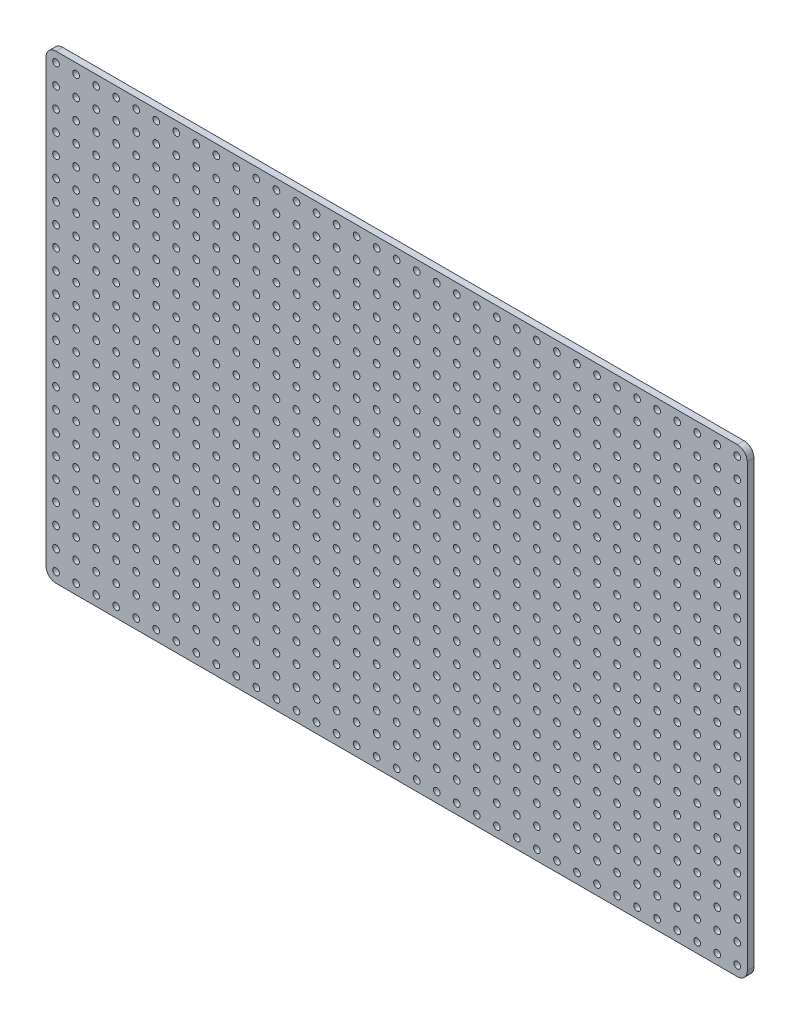
SolidWorks part; units mm, degrees
ref_plane "Alzado" through (0, 0, 0) normal (0, 0, 1) x (1, 0, 0)
ref_plane "Planta" through (0, 0, 0) normal (0, 1, 0) x (1, 0, 0)
ref_plane "Vista lateral" through (0, 0, 0) normal (1, 0, 0) x (0, 0, -1)
sketch "Model" plane through (0, 0, 0) normal (0, 0, 1) x (1, 0, 0)
  line L0 (256.4291, 471.7422) -> (562.4291, 471.7422)
  line L1 (256.4291, 264.7422) -> (562.4291, 264.7422)
  line L2 (251.9291, 269.2422) -> (251.9291, 467.2422)
  line L3 (566.9291, 467.2422) -> (566.9291, 269.2422)
  arc A0 (566.9291, 467.2422) -> (562.4291, 471.7422) centre (562.4291, 467.2422) ccw
  arc A1 (256.4291, 471.7422) -> (251.9291, 467.2422) centre (256.4291, 467.2422) ccw
  arc A2 (562.4291, 264.7422) -> (566.9291, 269.2422) centre (562.4291, 269.2422) ccw
  arc A3 (251.9291, 269.2422) -> (256.4291, 264.7422) centre (256.4291, 269.2422) ccw
  circle A4 centre (256.4291, 467.2422) radius 1.5
  circle A5 centre (256.4291, 458.2422) radius 1.5
  circle A6 centre (256.4291, 449.2422) radius 1.5
  circle A7 centre (256.4291, 440.2422) radius 1.5
  circle A8 centre (256.4291, 431.2422) radius 1.5
  circle A9 centre (256.4291, 422.2422) radius 1.5
  circle A10 centre (256.4291, 413.2422) radius 1.5
  circle A11 centre (256.4291, 404.2422) radius 1.5
  circle A12 centre (256.4291, 395.2422) radius 1.5
  circle A13 centre (256.4291, 386.2422) radius 1.5
  circle A14 centre (256.4291, 377.2422) radius 1.5
  circle A15 centre (256.4291, 368.2422) radius 1.5
  circle A16 centre (256.4291, 359.2422) radius 1.5
  circle A17 centre (256.4291, 350.2422) radius 1.5
  circle A18 centre (256.4291, 341.2422) radius 1.5
  circle A19 centre (256.4291, 332.2422) radius 1.5
  circle A20 centre (256.4291, 323.2422) radius 1.5
  circle A21 centre (256.4291, 314.2422) radius 1.5
  circle A22 centre (256.4291, 305.2422) radius 1.5
  circle A23 centre (265.4291, 467.2422) radius 1.5
  circle A24 centre (265.4291, 458.2422) radius 1.5
  circle A25 centre (265.4291, 449.2422) radius 1.5
  circle A26 centre (265.4291, 440.2422) radius 1.5
  circle A27 centre (265.4291, 431.2422) radius 1.5
  circle A28 centre (265.4291, 422.2422) radius 1.5
  circle A29 centre (265.4291, 413.2422) radius 1.5
  circle A30 centre (265.4291, 404.2422) radius 1.5
  circle A31 centre (265.4291, 395.2422) radius 1.5
  circle A32 centre (265.4291, 386.2422) radius 1.5
  circle A33 centre (265.4291, 377.2422) radius 1.5
  circle A34 centre (265.4291, 368.2422) radius 1.5
  circle A35 centre (265.4291, 359.2422) radius 1.5
  circle A36 centre (265.4291, 350.2422) radius 1.5
  circle A37 centre (265.4291, 341.2422) radius 1.5
  circle A38 centre (265.4291, 332.2422) radius 1.5
  circle A39 centre (265.4291, 323.2422) radius 1.5
  circle A40 centre (265.4291, 314.2422) radius 1.5
  circle A41 centre (265.4291, 305.2422) radius 1.5
  circle A42 centre (274.4291, 467.2422) radius 1.5
  circle A43 centre (274.4291, 458.2422) radius 1.5
  circle A44 centre (274.4291, 449.2422) radius 1.5
  circle A45 centre (274.4291, 440.2422) radius 1.5
  circle A46 centre (274.4291, 431.2422) radius 1.5
  circle A47 centre (274.4291, 422.2422) radius 1.5
  circle A48 centre (274.4291, 413.2422) radius 1.5
  circle A49 centre (274.4291, 404.2422) radius 1.5
  circle A50 centre (274.4291, 395.2422) radius 1.5
  circle A51 centre (274.4291, 386.2422) radius 1.5
  circle A52 centre (274.4291, 377.2422) radius 1.5
  circle A53 centre (274.4291, 368.2422) radius 1.5
  circle A54 centre (274.4291, 359.2422) radius 1.5
  circle A55 centre (274.4291, 350.2422) radius 1.5
  circle A56 centre (274.4291, 341.2422) radius 1.5
  circle A57 centre (274.4291, 332.2422) radius 1.5
  circle A58 centre (274.4291, 323.2422) radius 1.5
  circle A59 centre (274.4291, 314.2422) radius 1.5
  circle A60 centre (274.4291, 305.2422) radius 1.5
  circle A61 centre (283.4291, 467.2422) radius 1.5
  circle A62 centre (283.4291, 458.2422) radius 1.5
  circle A63 centre (283.4291, 449.2422) radius 1.5
  circle A64 centre (283.4291, 440.2422) radius 1.5
  circle A65 centre (283.4291, 431.2422) radius 1.5
  circle A66 centre (283.4291, 422.2422) radius 1.5
  circle A67 centre (283.4291, 413.2422) radius 1.5
  circle A68 centre (283.4291, 404.2422) radius 1.5
  circle A69 centre (283.4291, 395.2422) radius 1.5
  circle A70 centre (283.4291, 386.2422) radius 1.5
  circle A71 centre (283.4291, 377.2422) radius 1.5
  circle A72 centre (283.4291, 368.2422) radius 1.5
  circle A73 centre (283.4291, 359.2422) radius 1.5
  circle A74 centre (283.4291, 350.2422) radius 1.5
  circle A75 centre (283.4291, 341.2422) radius 1.5
  circle A76 centre (283.4291, 332.2422) radius 1.5
  circle A77 centre (283.4291, 323.2422) radius 1.5
  circle A78 centre (283.4291, 314.2422) radius 1.5
  circle A79 centre (283.4291, 305.2422) radius 1.5
  circle A80 centre (292.4291, 467.2422) radius 1.5
  circle A81 centre (292.4291, 458.2422) radius 1.5
  circle A82 centre (292.4291, 449.2422) radius 1.5
  circle A83 centre (292.4291, 440.2422) radius 1.5
  circle A84 centre (292.4291, 431.2422) radius 1.5
  circle A85 centre (292.4291, 422.2422) radius 1.5
  circle A86 centre (292.4291, 413.2422) radius 1.5
  circle A87 centre (292.4291, 404.2422) radius 1.5
  circle A88 centre (292.4291, 395.2422) radius 1.5
  circle A89 centre (292.4291, 386.2422) radius 1.5
  circle A90 centre (292.4291, 377.2422) radius 1.5
  circle A91 centre (292.4291, 368.2422) radius 1.5
  circle A92 centre (292.4291, 359.2422) radius 1.5
  circle A93 centre (292.4291, 350.2422) radius 1.5
  circle A94 centre (292.4291, 341.2422) radius 1.5
  circle A95 centre (292.4291, 332.2422) radius 1.5
  circle A96 centre (292.4291, 323.2422) radius 1.5
  circle A97 centre (292.4291, 314.2422) radius 1.5
  circle A98 centre (292.4291, 305.2422) radius 1.5
  circle A99 centre (301.4291, 467.2422) radius 1.5
  circle A100 centre (301.4291, 458.2422) radius 1.5
  circle A101 centre (301.4291, 449.2422) radius 1.5
  circle A102 centre (301.4291, 440.2422) radius 1.5
  circle A103 centre (301.4291, 431.2422) radius 1.5
  circle A104 centre (301.4291, 422.2422) radius 1.5
  circle A105 centre (301.4291, 413.2422) radius 1.5
  circle A106 centre (301.4291, 404.2422) radius 1.5
  circle A107 centre (301.4291, 395.2422) radius 1.5
  circle A108 centre (301.4291, 386.2422) radius 1.5
  circle A109 centre (301.4291, 377.2422) radius 1.5
  circle A110 centre (301.4291, 368.2422) radius 1.5
  circle A111 centre (301.4291, 359.2422) radius 1.5
  circle A112 centre (301.4291, 350.2422) radius 1.5
  circle A113 centre (301.4291, 341.2422) radius 1.5
  circle A114 centre (301.4291, 332.2422) radius 1.5
  circle A115 centre (301.4291, 323.2422) radius 1.5
  circle A116 centre (301.4291, 314.2422) radius 1.5
  circle A117 centre (301.4291, 305.2422) radius 1.5
  circle A118 centre (310.4291, 467.2422) radius 1.5
  circle A119 centre (310.4291, 458.2422) radius 1.5
  circle A120 centre (310.4291, 449.2422) radius 1.5
  circle A121 centre (310.4291, 440.2422) radius 1.5
  circle A122 centre (310.4291, 431.2422) radius 1.5
  circle A123 centre (310.4291, 422.2422) radius 1.5
  circle A124 centre (310.4291, 413.2422) radius 1.5
  circle A125 centre (310.4291, 404.2422) radius 1.5
  circle A126 centre (310.4291, 395.2422) radius 1.5
  circle A127 centre (310.4291, 386.2422) radius 1.5
  circle A128 centre (310.4291, 377.2422) radius 1.5
  circle A129 centre (310.4291, 368.2422) radius 1.5
  circle A130 centre (310.4291, 359.2422) radius 1.5
  circle A131 centre (310.4291, 350.2422) radius 1.5
  circle A132 centre (310.4291, 341.2422) radius 1.5
  circle A133 centre (310.4291, 332.2422) radius 1.5
  circle A134 centre (310.4291, 323.2422) radius 1.5
  circle A135 centre (310.4291, 314.2422) radius 1.5
  circle A136 centre (310.4291, 305.2422) radius 1.5
  circle A137 centre (319.4291, 467.2422) radius 1.5
  circle A138 centre (319.4291, 458.2422) radius 1.5
  circle A139 centre (319.4291, 449.2422) radius 1.5
  circle A140 centre (319.4291, 440.2422) radius 1.5
  circle A141 centre (319.4291, 431.2422) radius 1.5
  circle A142 centre (319.4291, 422.2422) radius 1.5
  circle A143 centre (319.4291, 413.2422) radius 1.5
  circle A144 centre (319.4291, 404.2422) radius 1.5
  circle A145 centre (319.4291, 395.2422) radius 1.5
  circle A146 centre (319.4291, 386.2422) radius 1.5
  circle A147 centre (319.4291, 377.2422) radius 1.5
  circle A148 centre (319.4291, 368.2422) radius 1.5
  circle A149 centre (319.4291, 359.2422) radius 1.5
  circle A150 centre (319.4291, 350.2422) radius 1.5
  circle A151 centre (319.4291, 341.2422) radius 1.5
  circle A152 centre (319.4291, 332.2422) radius 1.5
  circle A153 centre (319.4291, 323.2422) radius 1.5
  circle A154 centre (319.4291, 314.2422) radius 1.5
  circle A155 centre (319.4291, 305.2422) radius 1.5
  circle A156 centre (328.4291, 467.2422) radius 1.5
  circle A157 centre (328.4291, 458.2422) radius 1.5
  circle A158 centre (328.4291, 449.2422) radius 1.5
  circle A159 centre (328.4291, 440.2422) radius 1.5
  circle A160 centre (328.4291, 431.2422) radius 1.5
  circle A161 centre (328.4291, 422.2422) radius 1.5
  circle A162 centre (328.4291, 413.2422) radius 1.5
  circle A163 centre (328.4291, 404.2422) radius 1.5
  circle A164 centre (328.4291, 395.2422) radius 1.5
  circle A165 centre (328.4291, 386.2422) radius 1.5
  circle A166 centre (328.4291, 377.2422) radius 1.5
  circle A167 centre (328.4291, 368.2422) radius 1.5
  circle A168 centre (328.4291, 359.2422) radius 1.5
  circle A169 centre (328.4291, 350.2422) radius 1.5
  circle A170 centre (328.4291, 341.2422) radius 1.5
  circle A171 centre (328.4291, 332.2422) radius 1.5
  circle A172 centre (328.4291, 323.2422) radius 1.5
  circle A173 centre (328.4291, 314.2422) radius 1.5
  circle A174 centre (328.4291, 305.2422) radius 1.5
  circle A175 centre (337.4291, 467.2422) radius 1.5
  circle A176 centre (337.4291, 458.2422) radius 1.5
  circle A177 centre (337.4291, 449.2422) radius 1.5
  circle A178 centre (337.4291, 440.2422) radius 1.5
  circle A179 centre (337.4291, 431.2422) radius 1.5
  circle A180 centre (337.4291, 422.2422) radius 1.5
  circle A181 centre (337.4291, 413.2422) radius 1.5
  circle A182 centre (337.4291, 404.2422) radius 1.5
  circle A183 centre (337.4291, 395.2422) radius 1.5
  circle A184 centre (337.4291, 386.2422) radius 1.5
  circle A185 centre (337.4291, 377.2422) radius 1.5
  circle A186 centre (337.4291, 368.2422) radius 1.5
  circle A187 centre (337.4291, 359.2422) radius 1.5
  circle A188 centre (337.4291, 350.2422) radius 1.5
  circle A189 centre (337.4291, 341.2422) radius 1.5
  circle A190 centre (337.4291, 332.2422) radius 1.5
  circle A191 centre (337.4291, 323.2422) radius 1.5
  circle A192 centre (337.4291, 314.2422) radius 1.5
  circle A193 centre (337.4291, 305.2422) radius 1.5
  circle A194 centre (346.4291, 467.2422) radius 1.5
  circle A195 centre (346.4291, 458.2422) radius 1.5
  circle A196 centre (346.4291, 449.2422) radius 1.5
  circle A197 centre (346.4291, 440.2422) radius 1.5
  circle A198 centre (346.4291, 431.2422) radius 1.5
  circle A199 centre (346.4291, 422.2422) radius 1.5
  circle A200 centre (346.4291, 413.2422) radius 1.5
  circle A201 centre (346.4291, 404.2422) radius 1.5
  circle A202 centre (346.4291, 395.2422) radius 1.5
  circle A203 centre (346.4291, 386.2422) radius 1.5
  circle A204 centre (346.4291, 377.2422) radius 1.5
  circle A205 centre (346.4291, 368.2422) radius 1.5
  circle A206 centre (346.4291, 359.2422) radius 1.5
  circle A207 centre (346.4291, 350.2422) radius 1.5
  circle A208 centre (346.4291, 341.2422) radius 1.5
  circle A209 centre (346.4291, 332.2422) radius 1.5
  circle A210 centre (346.4291, 323.2422) radius 1.5
  circle A211 centre (346.4291, 314.2422) radius 1.5
  circle A212 centre (346.4291, 305.2422) radius 1.5
  circle A213 centre (355.4291, 467.2422) radius 1.5
  circle A214 centre (355.4291, 458.2422) radius 1.5
  circle A215 centre (355.4291, 449.2422) radius 1.5
  circle A216 centre (355.4291, 440.2422) radius 1.5
  circle A217 centre (355.4291, 431.2422) radius 1.5
  circle A218 centre (355.4291, 422.2422) radius 1.5
  circle A219 centre (355.4291, 413.2422) radius 1.5
  circle A220 centre (355.4291, 404.2422) radius 1.5
  circle A221 centre (355.4291, 395.2422) radius 1.5
  circle A222 centre (355.4291, 386.2422) radius 1.5
  circle A223 centre (355.4291, 377.2422) radius 1.5
  circle A224 centre (355.4291, 368.2422) radius 1.5
  circle A225 centre (355.4291, 359.2422) radius 1.5
  circle A226 centre (355.4291, 350.2422) radius 1.5
  circle A227 centre (355.4291, 341.2422) radius 1.5
  circle A228 centre (355.4291, 332.2422) radius 1.5
  circle A229 centre (355.4291, 323.2422) radius 1.5
  circle A230 centre (355.4291, 314.2422) radius 1.5
  circle A231 centre (355.4291, 305.2422) radius 1.5
  circle A232 centre (364.4291, 467.2422) radius 1.5
  circle A233 centre (364.4291, 458.2422) radius 1.5
  circle A234 centre (364.4291, 449.2422) radius 1.5
  circle A235 centre (364.4291, 440.2422) radius 1.5
  circle A236 centre (364.4291, 431.2422) radius 1.5
  circle A237 centre (364.4291, 422.2422) radius 1.5
  circle A238 centre (364.4291, 413.2422) radius 1.5
  circle A239 centre (364.4291, 404.2422) radius 1.5
  circle A240 centre (364.4291, 395.2422) radius 1.5
  circle A241 centre (364.4291, 386.2422) radius 1.5
  circle A242 centre (364.4291, 377.2422) radius 1.5
  circle A243 centre (364.4291, 368.2422) radius 1.5
  circle A244 centre (364.4291, 359.2422) radius 1.5
  circle A245 centre (364.4291, 350.2422) radius 1.5
  circle A246 centre (364.4291, 341.2422) radius 1.5
  circle A247 centre (364.4291, 332.2422) radius 1.5
  circle A248 centre (364.4291, 323.2422) radius 1.5
  circle A249 centre (364.4291, 314.2422) radius 1.5
  circle A250 centre (364.4291, 305.2422) radius 1.5
  circle A251 centre (373.4291, 467.2422) radius 1.5
  circle A252 centre (373.4291, 458.2422) radius 1.5
  circle A253 centre (373.4291, 449.2422) radius 1.5
  circle A254 centre (373.4291, 440.2422) radius 1.5
  circle A255 centre (373.4291, 431.2422) radius 1.5
  circle A256 centre (373.4291, 422.2422) radius 1.5
  circle A257 centre (373.4291, 413.2422) radius 1.5
  circle A258 centre (373.4291, 404.2422) radius 1.5
  circle A259 centre (373.4291, 395.2422) radius 1.5
  circle A260 centre (373.4291, 386.2422) radius 1.5
  circle A261 centre (373.4291, 377.2422) radius 1.5
  circle A262 centre (373.4291, 368.2422) radius 1.5
  circle A263 centre (373.4291, 359.2422) radius 1.5
  circle A264 centre (373.4291, 350.2422) radius 1.5
  circle A265 centre (373.4291, 341.2422) radius 1.5
  circle A266 centre (373.4291, 332.2422) radius 1.5
  circle A267 centre (373.4291, 323.2422) radius 1.5
  circle A268 centre (373.4291, 314.2422) radius 1.5
  circle A269 centre (373.4291, 305.2422) radius 1.5
  circle A270 centre (382.4291, 467.2422) radius 1.5
  circle A271 centre (382.4291, 458.2422) radius 1.5
  circle A272 centre (382.4291, 449.2422) radius 1.5
  circle A273 centre (382.4291, 440.2422) radius 1.5
  circle A274 centre (382.4291, 431.2422) radius 1.5
  circle A275 centre (382.4291, 422.2422) radius 1.5
  circle A276 centre (382.4291, 413.2422) radius 1.5
  circle A277 centre (382.4291, 404.2422) radius 1.5
  circle A278 centre (382.4291, 395.2422) radius 1.5
  circle A279 centre (382.4291, 386.2422) radius 1.5
  circle A280 centre (382.4291, 377.2422) radius 1.5
  circle A281 centre (382.4291, 368.2422) radius 1.5
  circle A282 centre (382.4291, 359.2422) radius 1.5
  circle A283 centre (382.4291, 350.2422) radius 1.5
  circle A284 centre (382.4291, 341.2422) radius 1.5
  circle A285 centre (382.4291, 332.2422) radius 1.5
  circle A286 centre (382.4291, 323.2422) radius 1.5
  circle A287 centre (382.4291, 314.2422) radius 1.5
  circle A288 centre (382.4291, 305.2422) radius 1.5
  circle A289 centre (391.4291, 467.2422) radius 1.5
  circle A290 centre (391.4291, 458.2422) radius 1.5
  circle A291 centre (391.4291, 449.2422) radius 1.5
  circle A292 centre (391.4291, 440.2422) radius 1.5
  circle A293 centre (391.4291, 431.2422) radius 1.5
  circle A294 centre (391.4291, 422.2422) radius 1.5
  circle A295 centre (391.4291, 413.2422) radius 1.5
  circle A296 centre (391.4291, 404.2422) radius 1.5
  circle A297 centre (391.4291, 395.2422) radius 1.5
  circle A298 centre (391.4291, 386.2422) radius 1.5
  circle A299 centre (391.4291, 377.2422) radius 1.5
  circle A300 centre (391.4291, 368.2422) radius 1.5
  circle A301 centre (391.4291, 359.2422) radius 1.5
  circle A302 centre (391.4291, 350.2422) radius 1.5
  circle A303 centre (391.4291, 341.2422) radius 1.5
  circle A304 centre (391.4291, 332.2422) radius 1.5
  circle A305 centre (391.4291, 323.2422) radius 1.5
  circle A306 centre (391.4291, 314.2422) radius 1.5
  circle A307 centre (391.4291, 305.2422) radius 1.5
  circle A308 centre (400.4291, 467.2422) radius 1.5
  circle A309 centre (400.4291, 458.2422) radius 1.5
  circle A310 centre (400.4291, 449.2422) radius 1.5
  circle A311 centre (400.4291, 440.2422) radius 1.5
  circle A312 centre (400.4291, 431.2422) radius 1.5
  circle A313 centre (400.4291, 422.2422) radius 1.5
  circle A314 centre (400.4291, 413.2422) radius 1.5
  circle A315 centre (400.4291, 404.2422) radius 1.5
  circle A316 centre (400.4291, 395.2422) radius 1.5
  circle A317 centre (400.4291, 386.2422) radius 1.5
  circle A318 centre (400.4291, 377.2422) radius 1.5
  circle A319 centre (400.4291, 368.2422) radius 1.5
  circle A320 centre (400.4291, 359.2422) radius 1.5
  circle A321 centre (400.4291, 350.2422) radius 1.5
  circle A322 centre (400.4291, 341.2422) radius 1.5
  circle A323 centre (400.4291, 332.2422) radius 1.5
  circle A324 centre (400.4291, 323.2422) radius 1.5
  circle A325 centre (400.4291, 314.2422) radius 1.5
  circle A326 centre (400.4291, 305.2422) radius 1.5
  circle A327 centre (409.4291, 467.2422) radius 1.5
  circle A328 centre (409.4291, 458.2422) radius 1.5
  circle A329 centre (409.4291, 449.2422) radius 1.5
  circle A330 centre (409.4291, 440.2422) radius 1.5
  circle A331 centre (409.4291, 431.2422) radius 1.5
  circle A332 centre (409.4291, 422.2422) radius 1.5
  circle A333 centre (409.4291, 413.2422) radius 1.5
  circle A334 centre (409.4291, 404.2422) radius 1.5
  circle A335 centre (409.4291, 395.2422) radius 1.5
  circle A336 centre (409.4291, 386.2422) radius 1.5
  circle A337 centre (409.4291, 377.2422) radius 1.5
  circle A338 centre (409.4291, 368.2422) radius 1.5
  circle A339 centre (409.4291, 359.2422) radius 1.5
  circle A340 centre (409.4291, 350.2422) radius 1.5
  circle A341 centre (409.4291, 341.2422) radius 1.5
  circle A342 centre (409.4291, 332.2422) radius 1.5
  circle A343 centre (409.4291, 323.2422) radius 1.5
  circle A344 centre (409.4291, 314.2422) radius 1.5
  circle A345 centre (409.4291, 305.2422) radius 1.5
  circle A346 centre (418.4291, 467.2422) radius 1.5
  circle A347 centre (418.4291, 458.2422) radius 1.5
  circle A348 centre (418.4291, 449.2422) radius 1.5
  circle A349 centre (418.4291, 440.2422) radius 1.5
  circle A350 centre (418.4291, 431.2422) radius 1.5
  circle A351 centre (418.4291, 422.2422) radius 1.5
  circle A352 centre (418.4291, 413.2422) radius 1.5
  circle A353 centre (418.4291, 404.2422) radius 1.5
  circle A354 centre (418.4291, 395.2422) radius 1.5
  circle A355 centre (418.4291, 386.2422) radius 1.5
  circle A356 centre (418.4291, 377.2422) radius 1.5
  circle A357 centre (418.4291, 368.2422) radius 1.5
  circle A358 centre (418.4291, 359.2422) radius 1.5
  circle A359 centre (418.4291, 350.2422) radius 1.5
  circle A360 centre (418.4291, 341.2422) radius 1.5
  circle A361 centre (418.4291, 332.2422) radius 1.5
  circle A362 centre (418.4291, 323.2422) radius 1.5
  circle A363 centre (418.4291, 314.2422) radius 1.5
  circle A364 centre (418.4291, 305.2422) radius 1.5
  circle A365 centre (427.4291, 467.2422) radius 1.5
  circle A366 centre (427.4291, 458.2422) radius 1.5
  circle A367 centre (427.4291, 449.2422) radius 1.5
  circle A368 centre (427.4291, 440.2422) radius 1.5
  circle A369 centre (427.4291, 431.2422) radius 1.5
  circle A370 centre (427.4291, 422.2422) radius 1.5
  circle A371 centre (427.4291, 413.2422) radius 1.5
  circle A372 centre (427.4291, 404.2422) radius 1.5
  circle A373 centre (427.4291, 395.2422) radius 1.5
  circle A374 centre (427.4291, 386.2422) radius 1.5
  circle A375 centre (427.4291, 377.2422) radius 1.5
  circle A376 centre (427.4291, 368.2422) radius 1.5
  circle A377 centre (427.4291, 359.2422) radius 1.5
  circle A378 centre (427.4291, 350.2422) radius 1.5
  circle A379 centre (427.4291, 341.2422) radius 1.5
  circle A380 centre (427.4291, 332.2422) radius 1.5
  circle A381 centre (427.4291, 323.2422) radius 1.5
  circle A382 centre (427.4291, 314.2422) radius 1.5
  circle A383 centre (427.4291, 305.2422) radius 1.5
  circle A384 centre (436.4291, 467.2422) radius 1.5
  circle A385 centre (436.4291, 458.2422) radius 1.5
  circle A386 centre (436.4291, 449.2422) radius 1.5
  circle A387 centre (436.4291, 440.2422) radius 1.5
  circle A388 centre (436.4291, 431.2422) radius 1.5
  circle A389 centre (436.4291, 422.2422) radius 1.5
  circle A390 centre (436.4291, 413.2422) radius 1.5
  circle A391 centre (436.4291, 404.2422) radius 1.5
  circle A392 centre (436.4291, 395.2422) radius 1.5
  circle A393 centre (436.4291, 386.2422) radius 1.5
  circle A394 centre (436.4291, 377.2422) radius 1.5
  circle A395 centre (436.4291, 368.2422) radius 1.5
  circle A396 centre (436.4291, 359.2422) radius 1.5
  circle A397 centre (436.4291, 350.2422) radius 1.5
  circle A398 centre (436.4291, 341.2422) radius 1.5
  circle A399 centre (436.4291, 332.2422) radius 1.5
  circle A400 centre (436.4291, 323.2422) radius 1.5
  circle A401 centre (436.4291, 314.2422) radius 1.5
  circle A402 centre (436.4291, 305.2422) radius 1.5
  circle A403 centre (445.4291, 467.2422) radius 1.5
  circle A404 centre (445.4291, 458.2422) radius 1.5
  circle A405 centre (445.4291, 449.2422) radius 1.5
  circle A406 centre (445.4291, 440.2422) radius 1.5
  circle A407 centre (445.4291, 431.2422) radius 1.5
  circle A408 centre (445.4291, 422.2422) radius 1.5
  circle A409 centre (445.4291, 413.2422) radius 1.5
  circle A410 centre (445.4291, 404.2422) radius 1.5
  circle A411 centre (445.4291, 395.2422) radius 1.5
  circle A412 centre (445.4291, 386.2422) radius 1.5
  circle A413 centre (445.4291, 377.2422) radius 1.5
  circle A414 centre (445.4291, 368.2422) radius 1.5
  circle A415 centre (445.4291, 359.2422) radius 1.5
  circle A416 centre (445.4291, 350.2422) radius 1.5
  circle A417 centre (445.4291, 341.2422) radius 1.5
  circle A418 centre (445.4291, 332.2422) radius 1.5
  circle A419 centre (445.4291, 323.2422) radius 1.5
  circle A420 centre (445.4291, 314.2422) radius 1.5
  circle A421 centre (445.4291, 305.2422) radius 1.5
  circle A422 centre (454.4291, 467.2422) radius 1.5
  circle A423 centre (454.4291, 458.2422) radius 1.5
  circle A424 centre (454.4291, 449.2422) radius 1.5
  circle A425 centre (454.4291, 440.2422) radius 1.5
  circle A426 centre (454.4291, 431.2422) radius 1.5
  circle A427 centre (454.4291, 422.2422) radius 1.5
  circle A428 centre (454.4291, 413.2422) radius 1.5
  circle A429 centre (454.4291, 404.2422) radius 1.5
  circle A430 centre (454.4291, 395.2422) radius 1.5
  circle A431 centre (454.4291, 386.2422) radius 1.5
  circle A432 centre (454.4291, 377.2422) radius 1.5
  circle A433 centre (454.4291, 368.2422) radius 1.5
  circle A434 centre (454.4291, 359.2422) radius 1.5
  circle A435 centre (454.4291, 350.2422) radius 1.5
  circle A436 centre (454.4291, 341.2422) radius 1.5
  circle A437 centre (454.4291, 332.2422) radius 1.5
  circle A438 centre (454.4291, 323.2422) radius 1.5
  circle A439 centre (454.4291, 314.2422) radius 1.5
  circle A440 centre (454.4291, 305.2422) radius 1.5
  circle A441 centre (463.4291, 467.2422) radius 1.5
  circle A442 centre (463.4291, 458.2422) radius 1.5
  circle A443 centre (463.4291, 449.2422) radius 1.5
  circle A444 centre (463.4291, 440.2422) radius 1.5
  circle A445 centre (463.4291, 431.2422) radius 1.5
  circle A446 centre (463.4291, 422.2422) radius 1.5
  circle A447 centre (463.4291, 413.2422) radius 1.5
  circle A448 centre (463.4291, 404.2422) radius 1.5
  circle A449 centre (463.4291, 395.2422) radius 1.5
  circle A450 centre (463.4291, 386.2422) radius 1.5
  circle A451 centre (463.4291, 377.2422) radius 1.5
  circle A452 centre (463.4291, 368.2422) radius 1.5
  circle A453 centre (463.4291, 359.2422) radius 1.5
  circle A454 centre (463.4291, 350.2422) radius 1.5
  circle A455 centre (463.4291, 341.2422) radius 1.5
  circle A456 centre (463.4291, 332.2422) radius 1.5
  circle A457 centre (463.4291, 323.2422) radius 1.5
  circle A458 centre (463.4291, 314.2422) radius 1.5
  circle A459 centre (463.4291, 305.2422) radius 1.5
  circle A460 centre (472.4291, 467.2422) radius 1.5
  circle A461 centre (472.4291, 458.2422) radius 1.5
  circle A462 centre (472.4291, 449.2422) radius 1.5
  circle A463 centre (472.4291, 440.2422) radius 1.5
  circle A464 centre (472.4291, 431.2422) radius 1.5
  circle A465 centre (472.4291, 422.2422) radius 1.5
  circle A466 centre (472.4291, 413.2422) radius 1.5
  circle A467 centre (472.4291, 404.2422) radius 1.5
  circle A468 centre (472.4291, 395.2422) radius 1.5
  circle A469 centre (472.4291, 386.2422) radius 1.5
  circle A470 centre (472.4291, 377.2422) radius 1.5
  circle A471 centre (472.4291, 368.2422) radius 1.5
  circle A472 centre (472.4291, 359.2422) radius 1.5
  circle A473 centre (472.4291, 350.2422) radius 1.5
  circle A474 centre (472.4291, 341.2422) radius 1.5
  circle A475 centre (472.4291, 332.2422) radius 1.5
  circle A476 centre (472.4291, 323.2422) radius 1.5
  circle A477 centre (472.4291, 314.2422) radius 1.5
  circle A478 centre (472.4291, 305.2422) radius 1.5
  circle A479 centre (481.4291, 467.2422) radius 1.5
  circle A480 centre (481.4291, 458.2422) radius 1.5
  circle A481 centre (481.4291, 449.2422) radius 1.5
  circle A482 centre (481.4291, 440.2422) radius 1.5
  circle A483 centre (481.4291, 431.2422) radius 1.5
  circle A484 centre (481.4291, 422.2422) radius 1.5
  circle A485 centre (481.4291, 413.2422) radius 1.5
  circle A486 centre (481.4291, 404.2422) radius 1.5
  circle A487 centre (481.4291, 395.2422) radius 1.5
  circle A488 centre (481.4291, 386.2422) radius 1.5
  circle A489 centre (481.4291, 377.2422) radius 1.5
  circle A490 centre (481.4291, 368.2422) radius 1.5
  circle A491 centre (481.4291, 359.2422) radius 1.5
  circle A492 centre (481.4291, 350.2422) radius 1.5
  circle A493 centre (481.4291, 341.2422) radius 1.5
  circle A494 centre (481.4291, 332.2422) radius 1.5
  circle A495 centre (481.4291, 323.2422) radius 1.5
  circle A496 centre (481.4291, 314.2422) radius 1.5
  circle A497 centre (481.4291, 305.2422) radius 1.5
  circle A498 centre (490.4291, 467.2422) radius 1.5
  circle A499 centre (490.4291, 458.2422) radius 1.5
  circle A500 centre (490.4291, 449.2422) radius 1.5
  circle A501 centre (490.4291, 440.2422) radius 1.5
  circle A502 centre (490.4291, 431.2422) radius 1.5
  circle A503 centre (490.4291, 422.2422) radius 1.5
  circle A504 centre (490.4291, 413.2422) radius 1.5
  circle A505 centre (490.4291, 404.2422) radius 1.5
  circle A506 centre (490.4291, 395.2422) radius 1.5
  circle A507 centre (490.4291, 386.2422) radius 1.5
  circle A508 centre (490.4291, 377.2422) radius 1.5
  circle A509 centre (490.4291, 368.2422) radius 1.5
  circle A510 centre (490.4291, 359.2422) radius 1.5
  circle A511 centre (490.4291, 350.2422) radius 1.5
  circle A512 centre (490.4291, 341.2422) radius 1.5
  circle A513 centre (490.4291, 332.2422) radius 1.5
  circle A514 centre (490.4291, 323.2422) radius 1.5
  circle A515 centre (490.4291, 314.2422) radius 1.5
  circle A516 centre (490.4291, 305.2422) radius 1.5
  circle A517 centre (499.4291, 467.2422) radius 1.5
  circle A518 centre (499.4291, 458.2422) radius 1.5
  circle A519 centre (499.4291, 449.2422) radius 1.5
  circle A520 centre (499.4291, 440.2422) radius 1.5
  circle A521 centre (499.4291, 431.2422) radius 1.5
  circle A522 centre (499.4291, 422.2422) radius 1.5
  circle A523 centre (499.4291, 413.2422) radius 1.5
  circle A524 centre (499.4291, 404.2422) radius 1.5
  circle A525 centre (499.4291, 395.2422) radius 1.5
  circle A526 centre (499.4291, 386.2422) radius 1.5
  circle A527 centre (499.4291, 377.2422) radius 1.5
  circle A528 centre (499.4291, 368.2422) radius 1.5
  circle A529 centre (499.4291, 359.2422) radius 1.5
  circle A530 centre (499.4291, 350.2422) radius 1.5
  circle A531 centre (499.4291, 341.2422) radius 1.5
  circle A532 centre (499.4291, 332.2422) radius 1.5
  circle A533 centre (499.4291, 323.2422) radius 1.5
  circle A534 centre (499.4291, 314.2422) radius 1.5
  circle A535 centre (499.4291, 305.2422) radius 1.5
  circle A536 centre (508.4291, 467.2422) radius 1.5
  circle A537 centre (508.4291, 458.2422) radius 1.5
  circle A538 centre (508.4291, 449.2422) radius 1.5
  circle A539 centre (508.4291, 440.2422) radius 1.5
  circle A540 centre (508.4291, 431.2422) radius 1.5
  circle A541 centre (508.4291, 422.2422) radius 1.5
  circle A542 centre (508.4291, 413.2422) radius 1.5
  circle A543 centre (508.4291, 404.2422) radius 1.5
  circle A544 centre (508.4291, 395.2422) radius 1.5
  circle A545 centre (508.4291, 386.2422) radius 1.5
  circle A546 centre (508.4291, 377.2422) radius 1.5
  circle A547 centre (508.4291, 368.2422) radius 1.5
  circle A548 centre (508.4291, 359.2422) radius 1.5
  circle A549 centre (508.4291, 350.2422) radius 1.5
  circle A550 centre (508.4291, 341.2422) radius 1.5
  circle A551 centre (508.4291, 332.2422) radius 1.5
  circle A552 centre (508.4291, 323.2422) radius 1.5
  circle A553 centre (508.4291, 314.2422) radius 1.5
  circle A554 centre (508.4291, 305.2422) radius 1.5
  circle A555 centre (517.4291, 467.2422) radius 1.5
  circle A556 centre (517.4291, 458.2422) radius 1.5
  circle A557 centre (517.4291, 449.2422) radius 1.5
  circle A558 centre (517.4291, 440.2422) radius 1.5
  circle A559 centre (517.4291, 431.2422) radius 1.5
  circle A560 centre (517.4291, 422.2422) radius 1.5
  circle A561 centre (517.4291, 413.2422) radius 1.5
  circle A562 centre (517.4291, 404.2422) radius 1.5
  circle A563 centre (517.4291, 395.2422) radius 1.5
  circle A564 centre (517.4291, 386.2422) radius 1.5
  circle A565 centre (517.4291, 377.2422) radius 1.5
  circle A566 centre (517.4291, 368.2422) radius 1.5
  circle A567 centre (517.4291, 359.2422) radius 1.5
  circle A568 centre (517.4291, 350.2422) radius 1.5
  circle A569 centre (517.4291, 341.2422) radius 1.5
  circle A570 centre (517.4291, 332.2422) radius 1.5
  circle A571 centre (517.4291, 323.2422) radius 1.5
  circle A572 centre (517.4291, 314.2422) radius 1.5
  circle A573 centre (517.4291, 305.2422) radius 1.5
  circle A574 centre (256.4291, 296.2422) radius 1.5
  circle A575 centre (256.4291, 287.2422) radius 1.5
  circle A576 centre (256.4291, 278.2422) radius 1.5
  circle A577 centre (265.4291, 296.2422) radius 1.5
  circle A578 centre (265.4291, 287.2422) radius 1.5
  circle A579 centre (265.4291, 278.2422) radius 1.5
  circle A580 centre (274.4291, 296.2422) radius 1.5
  circle A581 centre (274.4291, 287.2422) radius 1.5
  circle A582 centre (274.4291, 278.2422) radius 1.5
  circle A583 centre (283.4291, 296.2422) radius 1.5
  circle A584 centre (283.4291, 287.2422) radius 1.5
  circle A585 centre (283.4291, 278.2422) radius 1.5
  circle A586 centre (292.4291, 296.2422) radius 1.5
  circle A587 centre (292.4291, 287.2422) radius 1.5
  circle A588 centre (292.4291, 278.2422) radius 1.5
  circle A589 centre (301.4291, 296.2422) radius 1.5
  circle A590 centre (301.4291, 287.2422) radius 1.5
  circle A591 centre (301.4291, 278.2422) radius 1.5
  circle A592 centre (310.4291, 296.2422) radius 1.5
  circle A593 centre (310.4291, 287.2422) radius 1.5
  circle A594 centre (310.4291, 278.2422) radius 1.5
  circle A595 centre (319.4291, 296.2422) radius 1.5
  circle A596 centre (319.4291, 287.2422) radius 1.5
  circle A597 centre (319.4291, 278.2422) radius 1.5
  circle A598 centre (328.4291, 296.2422) radius 1.5
  circle A599 centre (328.4291, 287.2422) radius 1.5
  circle A600 centre (328.4291, 278.2422) radius 1.5
  circle A601 centre (337.4291, 296.2422) radius 1.5
  circle A602 centre (337.4291, 287.2422) radius 1.5
  circle A603 centre (337.4291, 278.2422) radius 1.5
  circle A604 centre (346.4291, 296.2422) radius 1.5
  circle A605 centre (346.4291, 287.2422) radius 1.5
  circle A606 centre (346.4291, 278.2422) radius 1.5
  circle A607 centre (355.4291, 296.2422) radius 1.5
  circle A608 centre (355.4291, 287.2422) radius 1.5
  circle A609 centre (355.4291, 278.2422) radius 1.5
  circle A610 centre (364.4291, 296.2422) radius 1.5
  circle A611 centre (364.4291, 287.2422) radius 1.5
  circle A612 centre (364.4291, 278.2422) radius 1.5
  circle A613 centre (373.4291, 296.2422) radius 1.5
  circle A614 centre (373.4291, 287.2422) radius 1.5
  circle A615 centre (373.4291, 278.2422) radius 1.5
  circle A616 centre (382.4291, 296.2422) radius 1.5
  circle A617 centre (382.4291, 287.2422) radius 1.5
  circle A618 centre (382.4291, 278.2422) radius 1.5
  circle A619 centre (391.4291, 296.2422) radius 1.5
  circle A620 centre (391.4291, 287.2422) radius 1.5
  circle A621 centre (391.4291, 278.2422) radius 1.5
  circle A622 centre (400.4291, 296.2422) radius 1.5
  circle A623 centre (400.4291, 287.2422) radius 1.5
  circle A624 centre (400.4291, 278.2422) radius 1.5
  circle A625 centre (409.4291, 296.2422) radius 1.5
  circle A626 centre (409.4291, 287.2422) radius 1.5
  circle A627 centre (409.4291, 278.2422) radius 1.5
  circle A628 centre (418.4291, 296.2422) radius 1.5
  circle A629 centre (418.4291, 287.2422) radius 1.5
  circle A630 centre (418.4291, 278.2422) radius 1.5
  circle A631 centre (427.4291, 296.2422) radius 1.5
  circle A632 centre (427.4291, 287.2422) radius 1.5
  circle A633 centre (427.4291, 278.2422) radius 1.5
  circle A634 centre (436.4291, 296.2422) radius 1.5
  circle A635 centre (436.4291, 287.2422) radius 1.5
  circle A636 centre (436.4291, 278.2422) radius 1.5
  circle A637 centre (445.4291, 296.2422) radius 1.5
  circle A638 centre (445.4291, 287.2422) radius 1.5
  circle A639 centre (445.4291, 278.2422) radius 1.5
  circle A640 centre (454.4291, 296.2422) radius 1.5
  circle A641 centre (454.4291, 287.2422) radius 1.5
  circle A642 centre (454.4291, 278.2422) radius 1.5
  circle A643 centre (463.4291, 296.2422) radius 1.5
  circle A644 centre (463.4291, 287.2422) radius 1.5
  circle A645 centre (463.4291, 278.2422) radius 1.5
  circle A646 centre (472.4291, 296.2422) radius 1.5
  circle A647 centre (472.4291, 287.2422) radius 1.5
  circle A648 centre (472.4291, 278.2422) radius 1.5
  circle A649 centre (481.4291, 296.2422) radius 1.5
  circle A650 centre (481.4291, 287.2422) radius 1.5
  circle A651 centre (481.4291, 278.2422) radius 1.5
  circle A652 centre (490.4291, 296.2422) radius 1.5
  circle A653 centre (490.4291, 287.2422) radius 1.5
  circle A654 centre (490.4291, 278.2422) radius 1.5
  circle A655 centre (499.4291, 296.2422) radius 1.5
  circle A656 centre (499.4291, 287.2422) radius 1.5
  circle A657 centre (499.4291, 278.2422) radius 1.5
  circle A658 centre (508.4291, 296.2422) radius 1.5
  circle A659 centre (508.4291, 287.2422) radius 1.5
  circle A660 centre (508.4291, 278.2422) radius 1.5
  circle A661 centre (517.4291, 296.2422) radius 1.5
  circle A662 centre (517.4291, 287.2422) radius 1.5
  circle A663 centre (517.4291, 278.2422) radius 1.5
  circle A664 centre (256.4291, 269.2422) radius 1.5
  circle A665 centre (265.4291, 269.2422) radius 1.5
  circle A666 centre (274.4291, 269.2422) radius 1.5
  circle A667 centre (283.4291, 269.2422) radius 1.5
  circle A668 centre (292.4291, 269.2422) radius 1.5
  circle A669 centre (301.4291, 269.2422) radius 1.5
  circle A670 centre (310.4291, 269.2422) radius 1.5
  circle A671 centre (319.4291, 269.2422) radius 1.5
  circle A672 centre (328.4291, 269.2422) radius 1.5
  circle A673 centre (337.4291, 269.2422) radius 1.5
  circle A674 centre (346.4291, 269.2422) radius 1.5
  circle A675 centre (355.4291, 269.2422) radius 1.5
  circle A676 centre (364.4291, 269.2422) radius 1.5
  circle A677 centre (373.4291, 269.2422) radius 1.5
  circle A678 centre (382.4291, 269.2422) radius 1.5
  circle A679 centre (391.4291, 269.2422) radius 1.5
  circle A680 centre (400.4291, 269.2422) radius 1.5
  circle A681 centre (409.4291, 269.2422) radius 1.5
  circle A682 centre (418.4291, 269.2422) radius 1.5
  circle A683 centre (427.4291, 269.2422) radius 1.5
  circle A684 centre (436.4291, 269.2422) radius 1.5
  circle A685 centre (445.4291, 269.2422) radius 1.5
  circle A686 centre (454.4291, 269.2422) radius 1.5
  circle A687 centre (463.4291, 269.2422) radius 1.5
  circle A688 centre (472.4291, 269.2422) radius 1.5
  circle A689 centre (481.4291, 269.2422) radius 1.5
  circle A690 centre (490.4291, 269.2422) radius 1.5
  circle A691 centre (499.4291, 269.2422) radius 1.5
  circle A692 centre (508.4291, 269.2422) radius 1.5
  circle A693 centre (517.4291, 269.2422) radius 1.5
  circle A694 centre (526.4291, 467.2422) radius 1.5
  circle A695 centre (526.4291, 458.2422) radius 1.5
  circle A696 centre (526.4291, 449.2422) radius 1.5
  circle A697 centre (526.4291, 440.2422) radius 1.5
  circle A698 centre (526.4291, 431.2422) radius 1.5
  circle A699 centre (526.4291, 422.2422) radius 1.5
  circle A700 centre (526.4291, 413.2422) radius 1.5
  circle A701 centre (526.4291, 404.2422) radius 1.5
  circle A702 centre (526.4291, 395.2422) radius 1.5
  circle A703 centre (526.4291, 386.2422) radius 1.5
  circle A704 centre (526.4291, 377.2422) radius 1.5
  circle A705 centre (526.4291, 368.2422) radius 1.5
  circle A706 centre (526.4291, 359.2422) radius 1.5
  circle A707 centre (526.4291, 350.2422) radius 1.5
  circle A708 centre (526.4291, 341.2422) radius 1.5
  circle A709 centre (526.4291, 332.2422) radius 1.5
  circle A710 centre (526.4291, 323.2422) radius 1.5
  circle A711 centre (526.4291, 314.2422) radius 1.5
  circle A712 centre (526.4291, 305.2422) radius 1.5
  circle A713 centre (535.4291, 467.2422) radius 1.5
  circle A714 centre (535.4291, 458.2422) radius 1.5
  circle A715 centre (535.4291, 449.2422) radius 1.5
  circle A716 centre (535.4291, 440.2422) radius 1.5
  circle A717 centre (535.4291, 431.2422) radius 1.5
  circle A718 centre (535.4291, 422.2422) radius 1.5
  circle A719 centre (535.4291, 413.2422) radius 1.5
  circle A720 centre (535.4291, 404.2422) radius 1.5
  circle A721 centre (535.4291, 395.2422) radius 1.5
  circle A722 centre (535.4291, 386.2422) radius 1.5
  circle A723 centre (535.4291, 377.2422) radius 1.5
  circle A724 centre (535.4291, 368.2422) radius 1.5
  circle A725 centre (535.4291, 359.2422) radius 1.5
  circle A726 centre (535.4291, 350.2422) radius 1.5
  circle A727 centre (535.4291, 341.2422) radius 1.5
  circle A728 centre (535.4291, 332.2422) radius 1.5
  circle A729 centre (535.4291, 323.2422) radius 1.5
  circle A730 centre (535.4291, 314.2422) radius 1.5
  circle A731 centre (535.4291, 305.2422) radius 1.5
  circle A732 centre (544.4291, 467.2422) radius 1.5
  circle A733 centre (544.4291, 458.2422) radius 1.5
  circle A734 centre (544.4291, 449.2422) radius 1.5
  circle A735 centre (544.4291, 440.2422) radius 1.5
  circle A736 centre (544.4291, 431.2422) radius 1.5
  circle A737 centre (544.4291, 422.2422) radius 1.5
  circle A738 centre (544.4291, 413.2422) radius 1.5
  circle A739 centre (544.4291, 404.2422) radius 1.5
  circle A740 centre (544.4291, 395.2422) radius 1.5
  circle A741 centre (544.4291, 386.2422) radius 1.5
  circle A742 centre (544.4291, 377.2422) radius 1.5
  circle A743 centre (544.4291, 368.2422) radius 1.5
  circle A744 centre (544.4291, 359.2422) radius 1.5
  circle A745 centre (544.4291, 350.2422) radius 1.5
  circle A746 centre (544.4291, 341.2422) radius 1.5
  circle A747 centre (544.4291, 332.2422) radius 1.5
  circle A748 centre (544.4291, 323.2422) radius 1.5
  circle A749 centre (544.4291, 314.2422) radius 1.5
  circle A750 centre (544.4291, 305.2422) radius 1.5
  circle A751 centre (553.4291, 467.2422) radius 1.5
  circle A752 centre (553.4291, 458.2422) radius 1.5
  circle A753 centre (553.4291, 449.2422) radius 1.5
  circle A754 centre (553.4291, 440.2422) radius 1.5
  circle A755 centre (553.4291, 431.2422) radius 1.5
  circle A756 centre (553.4291, 422.2422) radius 1.5
  circle A757 centre (553.4291, 413.2422) radius 1.5
  circle A758 centre (553.4291, 404.2422) radius 1.5
  circle A759 centre (553.4291, 395.2422) radius 1.5
  circle A760 centre (553.4291, 386.2422) radius 1.5
  circle A761 centre (553.4291, 377.2422) radius 1.5
  circle A762 centre (553.4291, 368.2422) radius 1.5
  circle A763 centre (553.4291, 359.2422) radius 1.5
  circle A764 centre (553.4291, 350.2422) radius 1.5
  circle A765 centre (553.4291, 341.2422) radius 1.5
  circle A766 centre (553.4291, 332.2422) radius 1.5
  circle A767 centre (553.4291, 323.2422) radius 1.5
  circle A768 centre (553.4291, 314.2422) radius 1.5
  circle A769 centre (553.4291, 305.2422) radius 1.5
  circle A770 centre (526.4291, 296.2422) radius 1.5
  circle A771 centre (526.4291, 287.2422) radius 1.5
  circle A772 centre (526.4291, 278.2422) radius 1.5
  circle A773 centre (535.4291, 296.2422) radius 1.5
  circle A774 centre (535.4291, 287.2422) radius 1.5
  circle A775 centre (535.4291, 278.2422) radius 1.5
  circle A776 centre (544.4291, 296.2422) radius 1.5
  circle A777 centre (544.4291, 287.2422) radius 1.5
  circle A778 centre (544.4291, 278.2422) radius 1.5
  circle A779 centre (553.4291, 296.2422) radius 1.5
  circle A780 centre (553.4291, 287.2422) radius 1.5
  circle A781 centre (553.4291, 278.2422) radius 1.5
  circle A782 centre (526.4291, 269.2422) radius 1.5
  circle A783 centre (535.4291, 269.2422) radius 1.5
  circle A784 centre (544.4291, 269.2422) radius 1.5
  circle A785 centre (553.4291, 269.2422) radius 1.5
  circle A786 centre (562.4291, 467.2422) radius 1.5
  circle A787 centre (562.4291, 458.2422) radius 1.5
  circle A788 centre (562.4291, 449.2422) radius 1.5
  circle A789 centre (562.4291, 440.2422) radius 1.5
  circle A790 centre (562.4291, 431.2422) radius 1.5
  circle A791 centre (562.4291, 422.2422) radius 1.5
  circle A792 centre (562.4291, 413.2422) radius 1.5
  circle A793 centre (562.4291, 404.2422) radius 1.5
  circle A794 centre (562.4291, 395.2422) radius 1.5
  circle A795 centre (562.4291, 386.2422) radius 1.5
  circle A796 centre (562.4291, 377.2422) radius 1.5
  circle A797 centre (562.4291, 368.2422) radius 1.5
  circle A798 centre (562.4291, 359.2422) radius 1.5
  circle A799 centre (562.4291, 350.2422) radius 1.5
  circle A800 centre (562.4291, 341.2422) radius 1.5
  circle A801 centre (562.4291, 332.2422) radius 1.5
  circle A802 centre (562.4291, 323.2422) radius 1.5
  circle A803 centre (562.4291, 314.2422) radius 1.5
  circle A804 centre (562.4291, 305.2422) radius 1.5
  circle A805 centre (562.4291, 296.2422) radius 1.5
  circle A806 centre (562.4291, 287.2422) radius 1.5
  circle A807 centre (562.4291, 278.2422) radius 1.5
  circle A808 centre (562.4291, 269.2422) radius 1.5
extrude "Saliente-Extruir1" add sketch "Model" along normal blind 3
